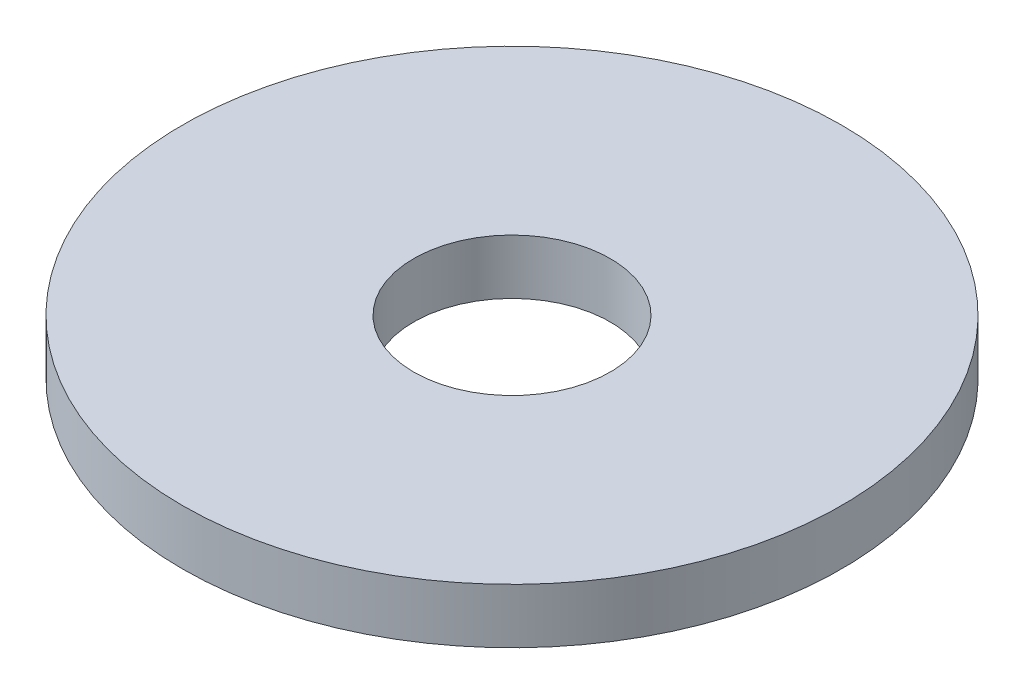
SolidWorks part; units mm, degrees
material "Plain Carbon Steel"
ref_plane "Front Plane" through (0, 0, 0) normal (0, 0, 1) x (1, 0, 0)
ref_plane "Top Plane" through (0, 0, 0) normal (0, 1, 0) x (1, 0, 0)
ref_plane "Right Plane" through (0, 0, 0) normal (1, 0, 0) x (0, 0, -1)
sketch "Sketch1" plane through (0, 0, 0) normal (0, 1, 0) x (1, 0, 0)
  circle A0 centre (0, 0) radius 11.3665
  circle A1 centre (0, 0) radius 38.1
  dimension "D1" = 22.733
  dimension "D2" = 76.2
extrude "Boss-Extrude1" add sketch "Sketch1" along normal blind 6.35
